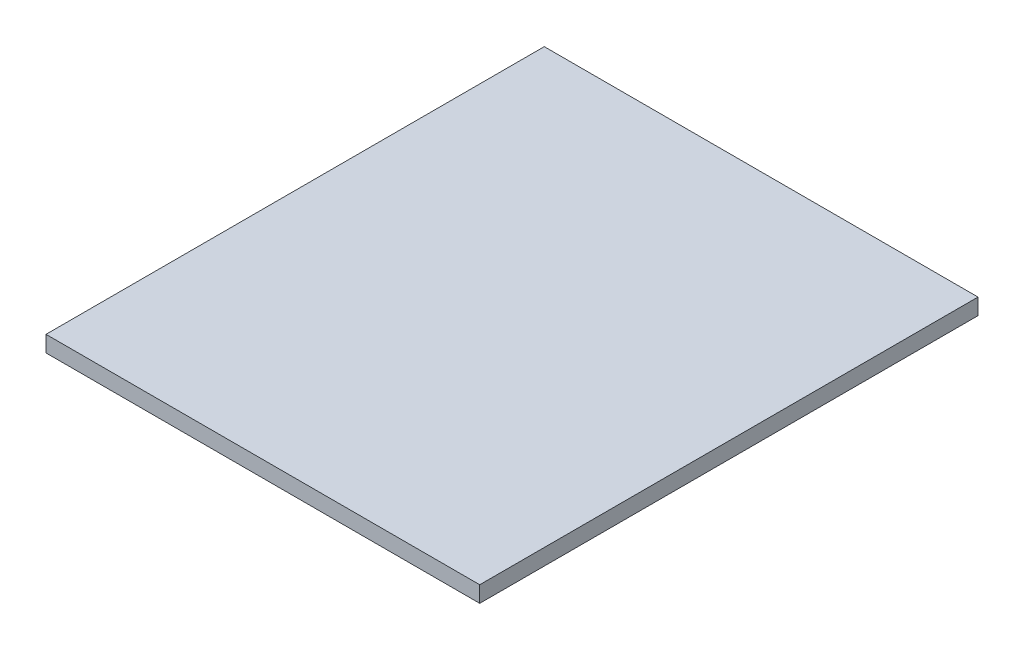
SolidWorks part; units mm, degrees
ref_plane "Front Plane" through (0, 0, 0) normal (0, 0, 1) x (1, 0, 0)
ref_plane "Top Plane" through (0, 0, 0) normal (0, 1, 0) x (1, 0, 0)
ref_plane "Right Plane" through (0, 0, 0) normal (1, 0, 0) x (0, 0, -1)
sketch "Sketch1" plane through (0, 0, 0) normal (0, 1, 0) x (1, 0, 0)
  line L1 (-44.2815, 20.698) -> (41.7185, 20.698)
  line L2 (-44.2815, 20.698) -> (-44.2815, -78.102)
  line L3 (-44.2815, -78.102) -> (41.7185, -78.102)
  line L4 (41.7185, 20.698) -> (41.7185, -78.102)
  dimension "D1" = 86
  dimension "D2" = 98.8
extrude "Boss-Extrude1" add sketch "Sketch1" along normal blind 3.2
equation "\"Fit\"= 1"
equation "\"cover width\" = 98.8"
equation "\"bottom 2 length\"= 86"
equation "\"thinner acrylic\"= 3.2"
equation "\"D1@Sketch1\"=\"bottom 2 length\""
equation "\"D2@Sketch1\"=\"cover width\""
equation "\"D1@Boss-Extrude1\"=\"thinner acrylic\""
